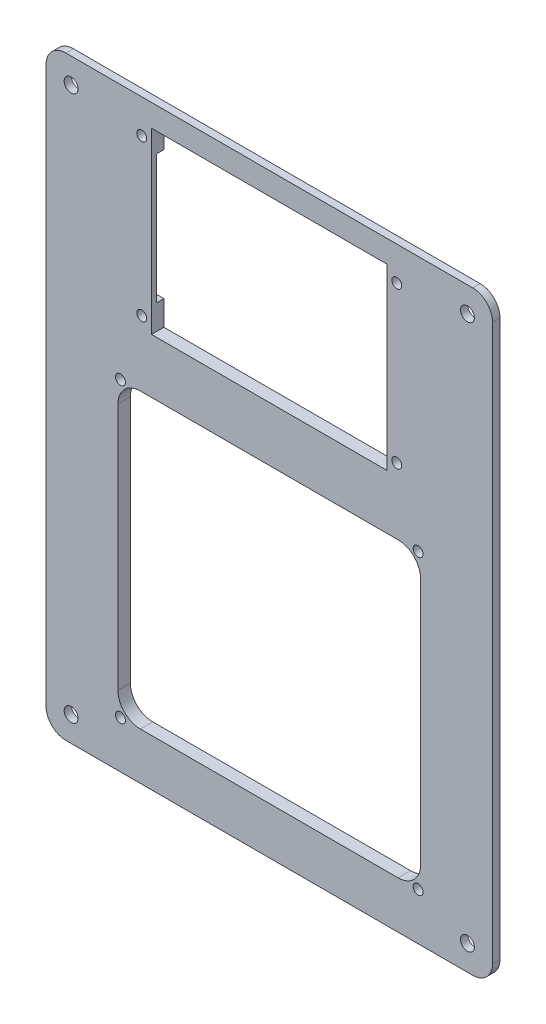
SolidWorks part; units mm, degrees
ref_plane "Front Plane" through (0, 0, 0) normal (0, 0, 1) x (1, 0, 0)
ref_plane "Top Plane" through (0, 0, 0) normal (0, 1, 0) x (1, 0, 0)
ref_plane "Right Plane" through (0, 0, 0) normal (1, 0, 0) x (0, 0, -1)
sketch "Sketch1" plane through (0, 0, 0) normal (0, 0, 1) x (1, 0, 0)
  line L1 (-45, 60) -> (45, 60)
  line L2 (-45, 60) -> (-45, -60)
  line L3 (-45, -60) -> (45, -60)
  line L4 (45, 60) -> (45, -60)
  line L5 (-45, 60) -> (45, -60) construction
  line L6 (-45, -60) -> (45, 60) construction
  point P0 (0, 0)
  dimension "D1" = 120
  dimension "D2" = 90
extrude "Boss-Extrude1" add sketch "Sketch1" along normal blind 2.5
sketch "Sketch2" plane through (0, 0, 2.5) normal (0, 0, 1) x (1, 0, 0)
  line L0 (0, -60) -> (0, -50.5)
  line L1 (-45, -60) -> (45, -60) construction
  line L2 (0, -50.5) -> (-30.5, -50.5)
  line L3 (-30.5, -50.5) -> (-30.5, 8.5)
  line L4 (-30.5, 8.5) -> (30.5, 8.5)
  line L5 (30.5, 8.5) -> (30.5, -50.5)
  line L6 (30.5, -50.5) -> (0, -50.5)
  line L7 (0, 60) -> (0, 55.5)
  line L8 (45, 60) -> (-45, 60) construction
  line L9 (0, 55.5) -> (23.75, 55.5)
  line L10 (23.75, 55.5) -> (23.75, 19.5)
  line L11 (23.75, 19.5) -> (-23.75, 19.5)
  line L12 (-23.75, 19.5) -> (-23.75, 55.5)
  line L13 (-23.75, 55.5) -> (0, 55.5)
  line L14 (-23.75, 55.5) -> (-23.75, 51.5)
  line L15 (23.75, 19.5) -> (23.75, 23.8)
  line L16 (-25.7, 53.2) -> (25.7, 53.2)
  line L17 (-23.75, 19.5) -> (-23.75, 23.5)
  line L18 (-25.7, 53.2) -> (-25.7, 21.8)
  line L19 (-25.7, 21.8) -> (25.7, 21.8)
  line L20 (23.75, 19.5) -> (16.25, 19.5)
  line L21 (25.7, 53.2) -> (25.7, 21.8)
  line L22 (-25.7, 53.2) -> (25.7, 21.8) construction
  line L23 (0, -50.5) -> (-30.25, -50.5)
  line L27 (30, -50.5) -> (0, -50.5)
  line L28 (-25.7, 21.8) -> (25.7, 53.2) construction
  line L29 (23.75, 23.8) -> (25.7, 23.8)
  line L30 (23.75, 55.5) -> (23.75, 51.2)
  line L31 (23.75, 51.2) -> (25.7, 51.2)
  line L32 (25.7, 51.2) -> (25.7, 23.8)
  circle A0 centre (25.7, 21.8) radius 1
  circle A1 centre (25.7, 53.2) radius 1
  circle A2 centre (-25.7, 53.2) radius 1
  circle A3 centre (-25.7, 21.8) radius 1
  point P19 (0, 37.5)
  point P28 (25.7, 53.2)
  dimension "D7" = 2
  dimension "D8" = 2
  dimension "D9" = 2
  dimension "D10" = 2
  dimension "D1" = 9.5
  dimension "D3" = 59
  dimension "D4" = 61
  dimension "D5" = 31.4
  dimension "D6" = 51.4
  dimension "D11" = 4.3
  dimension "D12" = 4.3
extrude "Cut-Extrude2" cut sketch "Sketch2" against normal blind 10 contours L2 L6 | L9 L10 L11 L12 L13 | L2 L3 L4 L5 L6 region at (0, -21, 2.5)
sketch "Sketch4" plane through (0, 0, 0) normal (0, 0, -1) x (-1, 0, 0)
  line L1 (-43.2, 58.2) -> (43.2, 58.2)
  line L2 (-43.2, 58.2) -> (-43.2, -58.2)
  line L3 (-43.2, -58.2) -> (43.2, -58.2)
  line L4 (43.2, 58.2) -> (43.2, -58.2)
  line L5 (-43.2, 58.2) -> (43.2, -58.2) construction
  line L6 (-43.2, -58.2) -> (43.2, 58.2) construction
  line L7 (-45, 60) -> (45, 60)
  line L8 (-45, 60) -> (-45, -60)
  line L9 (-45, -60) -> (45, -60)
  line L10 (45, 60) -> (45, -60)
  point P0 (0, 0)
  dimension "D1" = 116.4
  dimension "D2" = 86.4
extrude "Cut-Extrude4" cut sketch "Sketch4" against normal blind 1
fillet "Fillet2" radius 4 8 edges at (-45, 60, 1.75) (45, 60, 1.75) (45, -60, 1.75) (-45, -60, 1.75) (-43.2, -58.2, 0.5) (43.2, -58.2, 0.5) (-43.2, 58.2, 0.5) (43.2, 58.2, 0.5)
fillet "Fillet3" radius 4.512 4 edges at (-30.5, -50.5, 1.25) (30.5, -50.5, 1.25) (30.5, 8.5, 1.25) (-30.5, 8.5, 1.25)
sketch "Sketch5" plane through (0, 0, 2.5) normal (0, 0, 1) x (1, 0, 0)
  line L0 (-30.5, -21) -> (-45, -21)
  line L1 (0, -50.5) -> (-30, -50.5)
  line L2 (-30.5, -45.988) -> (-30.5, 3.988) construction
  line L3 (-30, -50.5) -> (-30, 8.5)
  line L7 (25.988, -50.5) -> (-25.988, -50.5) construction
  line L8 (-45, 56) -> (-45, -56) construction
  line L9 (0, -50.5) -> (0, -60)
  line L10 (-41, -60) -> (41, -60) construction
  circle A0 centre (-30, 8.5) radius 1
  circle A1 centre (-30, -50.5) radius 1
  circle A2 centre (30, 8.5) radius 1
  circle A3 centre (30, -50.5) radius 1
  dimension "D3" = 2
  dimension "D4" = 2
  dimension "D1" = 30
  dimension "D2" = 59
extrude "Cut-Extrude6" cut sketch "Sketch2<4>" against normal blind 1.5 contours L16 A2 L18 | L18 A2 L16 | L18 A3 L19 | L19 A3 L18 | L19 A0 L21 | L21 A0 L19 | L21 A1 L16 | L16 A1 L21 region at (25.8415, 53.3415, 2.5) region at (25.2756, 52.7756, 2.5) region at (-25.2756, 52.7756, 2.5) region at (-25.8415, 53.3415, 2.5) region at (-25.2756, 22.2244, 2.5) region at (-25.8415, 21.6585, 2.5) region at (25.2756, 22.2244, 2.5) region at (25.8415, 21.6585, 2.5)
sketch "Sketch2<4>" plane through (0, 0, 2.5) normal (0, 0, 1) x (1, 0, 0) same geometry as "Sketch2"
extrude "Cut-Extrude9" cut sketch "Sketch5" against normal blind 1.5 contours A0 | A2 | A3 | L3 A1 L1 | L1 A1 L3 region at (-30.1415, -50.6415, 2.5) region at (-29.5756, -50.0756, 2.5) region at (-30.6871, 9.1871, 2.5) region at (30, 8.5, 2.5) region at (30, -50.5, 2.5)
sketch "Sketch6" plane through (0, 0, 2.5) normal (0, 0, 1) x (1, 0, 0)
  circle A0 centre (-30, 8.5) radius 1
extrude "Cut-Extrude10" cut sketch "Sketch6" against normal blind 5
sketch "Sketch7" plane through (0, 0, 2.5) normal (0, 0, 1) x (1, 0, 0)
  circle A0 centre (30, 8.5) radius 1
extrude "Cut-Extrude11" cut sketch "Sketch7" against normal blind 5
sketch "Sketch8" plane through (0, 0, 2.5) normal (0, 0, 1) x (1, 0, 0)
  circle A0 centre (-25.7, 21.8) radius 1
extrude "Cut-Extrude12" cut sketch "Sketch8" against normal blind 5
sketch "Sketch9" plane through (0, 0, 2.5) normal (0, 0, 1) x (1, 0, 0)
  circle A0 centre (25.7, 21.8) radius 1
extrude "Cut-Extrude13" cut sketch "Sketch9" against normal blind 5
sketch "Sketch10" plane through (0, 0, 2.5) normal (0, 0, 1) x (1, 0, 0)
  circle A0 centre (-30, -50.5) radius 1
extrude "Cut-Extrude14" cut sketch "Sketch10" against normal blind 5
sketch "Sketch11" plane through (0, 0, 2.5) normal (0, 0, 1) x (1, 0, 0)
  circle A0 centre (30, -50.5) radius 1
extrude "Cut-Extrude15" cut sketch "Sketch11" against normal blind 5
sketch "Sketch12" plane through (0, 0, 2.5) normal (0, 0, 1) x (1, 0, 0)
  circle A0 centre (25.7, 53.2) radius 1
extrude "Cut-Extrude16" cut sketch "Sketch12" against normal blind 5
sketch "Sketch13" plane through (0, 0, 2.5) normal (0, 0, 1) x (1, 0, 0)
  circle A0 centre (-25.7, 53.2) radius 1
extrude "Cut-Extrude17" cut sketch "Sketch13" against normal blind 5
sketch "ske_vat" plane through (0, 0, 0) normal (0, 0, -1) x (1, 0, 0)
  circle A2 centre (42.0284, -57.0284) radius 8
  arc A3 (39.2, -58.2) -> (43.2, -54.2) centre (39.2, -54.2) ccw construction
extrude "vat" cut sketch "ske_vat" against normal blind 1
ref_plane "Plane1" through (0, 0, 0) normal (0, 1, 0) x (1, 0, 0)
ref_plane "Plane2" through (0, 0, 0) normal (1, 0, 0) x (0, 0, -1)
mirror "Mirror1" about plane through (0, 0, 0) normal (1, 0, 0) of "vat"
mirror "Mirror2" about plane through (0, 0, 0) normal (0, 1, 0) of "vat"
mirror "Mirror3" about plane through (0, 0, 0) normal (1, 0, 0) of "Mirror2"
sketch "Sketch18" plane through (0, 0, 0) normal (0, 0, -1) x (1, 0, 0)
  line L2 (-23.75, -37.5) -> (-33.75, -37.5)
  line L3 (-23.75, -19.5) -> (-23.75, -55.5) construction
  line L4 (-33.75, -37.5) -> (-33.75, -24.5)
  line L5 (-33.75, -24.5) -> (-23.75, -24.5)
  line L6 (-23.75, -24.5) -> (-23.75, -50.5)
  line L7 (-23.75, -50.5) -> (-33.75, -50.5)
  line L8 (-33.75, -50.5) -> (-33.75, -37.5)
  line M26 (-23.75, -55.5) -> (-23.75, -19.5)
extrude "Cut-Extrude19" cut sketch "Sketch18" against normal blind 1.5 contours L5 L4 L2 M26 | L8 L7 L2 M26 region at (-28.75, 44, 0) region at (-28.75, 31, 0)
sketch "Sketch19" plane through (0, 0, 1) normal (0, 0, -1) x (1, 0, 0)
  line L0 (43.8284, -58.8284) -> (39.9393, -54.9393)
  arc A0 (41, -60) -> (45, -56) centre (41, -56) ccw construction
  circle A1 centre (39.9393, -54.9393) radius 1.4
extrude "Cut-Extrude20" cut sketch "Sketch19" against normal blind 10 contours A1 region at (41.1962, 55.4599, 1)
mirror "Mirror4" about plane through (0, 0, 0) normal (1, 0, 0) of "Cut-Extrude20"
mirror "Mirror5" about plane through (0, 0, 0) normal (0, 1, 0) of "Cut-Extrude20", "Mirror4"
